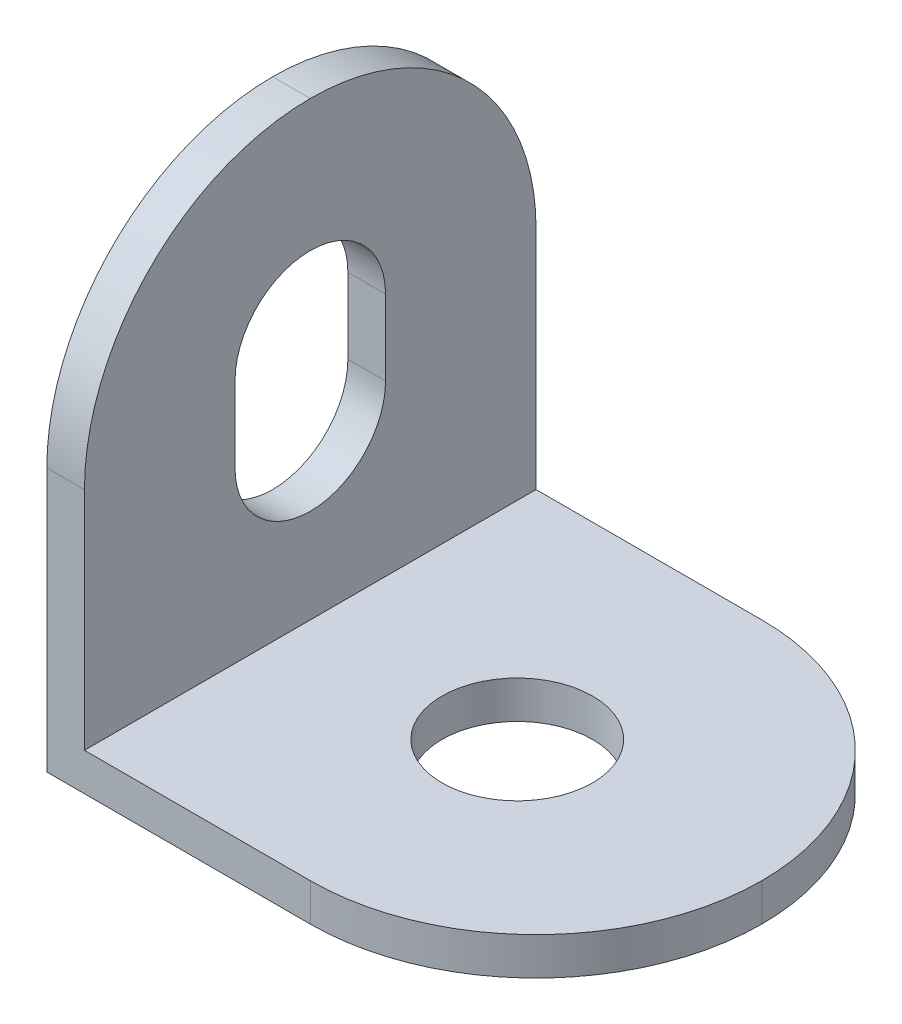
SolidWorks part; units mm, degrees
ref_plane "Front Plane" through (0, 0, 0) normal (0, 0, 1) x (1, 0, 0)
ref_plane "Top Plane" through (0, 0, 0) normal (0, 1, 0) x (1, 0, 0)
ref_plane "Right Plane" through (0, 0, 0) normal (1, 0, 0) x (0, 0, -1)
sketch "Sketch1" plane through (0, 0, 0) normal (0, 0, 1) x (1, 0, 0)
  line L0 (0, 0) -> (13, 0)
  line L1 (13, 0) -> (13, 1)
  line L2 (13, 1) -> (1, 1)
  line L3 (1, 1) -> (1, 13)
  line L4 (1, 13) -> (0, 13)
  line L5 (0, 13) -> (0, 0)
  dimension "D1" = 1
  dimension "D2" = 1
  dimension "D3" = 13
  dimension "D4" = 13
extrude "Boss-Extrude1" add sketch "Sketch1" along normal blind 12
sketch "Sketch2" plane through (0, 0, 0) normal (-1, 0, 0) x (0, 0, 1)
  line L0 (6, 5.5) -> (6, 7.5) construction
  line L1 (4, 5.5) -> (4, 7.5)
  line L2 (8, 5.5) -> (8, 7.5)
  line L3 (0, 13) -> (0, 0) construction
  line L4 (12, 0) -> (0, 0) construction
  arc A0 (4, 5.5) -> (8, 5.5) centre (6, 5.5) ccw
  arc A1 (8, 7.5) -> (4, 7.5) centre (6, 7.5) ccw
  point P2 (6, 6.5)
  dimension "D1" = 2
  dimension "D2" = 2
  dimension "D3" = 6
  dimension "D4" = 6.5
extrude "Cut-Extrude1" cut sketch "Sketch2" against normal through all
sketch "Sketch3" plane through (0, 0, 0) normal (0, -1, 0) x (1, 0, 0)
  line L0 (0, 12) -> (13, 12) construction
  circle A0 centre (6.5, 6) radius 2
  dimension "D1" = 4
  dimension "D2" = 6.5
  dimension "D3" = 6
extrude "Cut-Extrude2" cut sketch "Sketch3" against normal through all
fillet "Fillet1" radius 6 4 edges at (0.5, 13, 0) (13, 0.5, 0) (13, 0.5, 12) (0.5, 13, 12)
